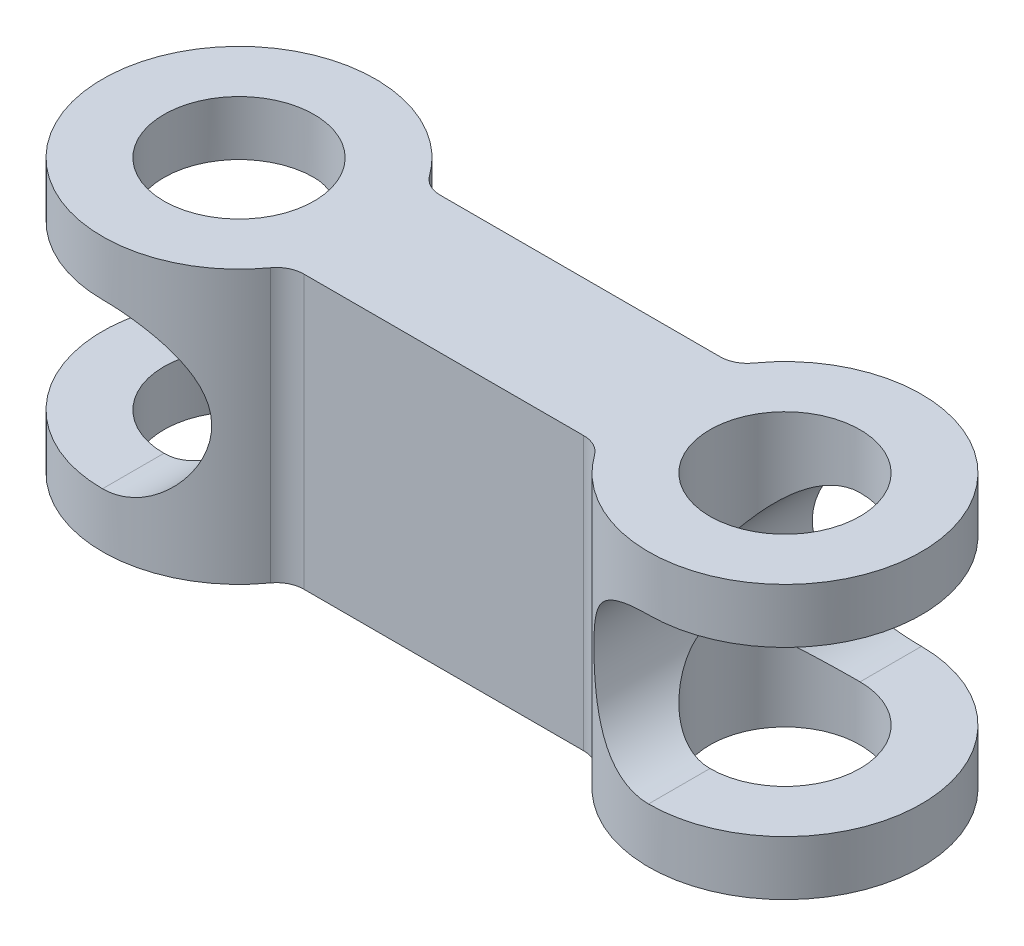
SolidWorks part; units mm, degrees
ref_plane "Front Plane" through (0, 0, 0) normal (0, 0, 1) x (1, 0, 0)
ref_plane "Top Plane" through (0, 0, 0) normal (0, 1, 0) x (1, 0, 0)
ref_plane "Right Plane" through (0, 0, 0) normal (1, 0, 0) x (0, 0, -1)
sketch "Sketch1" plane through (0, 0, 0) normal (0, 1, 0) x (1, 0, 0)
  line L1 (0, 2.5) -> (10, 2.5)
  line L2 (0, 2.5) -> (0, -2.5)
  line L3 (0, -2.5) -> (10, -2.5)
  line L4 (10, 2.5) -> (10, -2.5)
  dimension "D1" = 5
  dimension "D2" = 10
extrude "Boss-Extrude1" add sketch "Sketch1" along normal blind 10
sketch "Sketch2" plane through (0, 0, 0) normal (0, 1, 0) x (1, 0, 0)
  circle A0 centre (0, 0) radius 5
  dimension "D1" = 10
sketch "Sketch3" plane through (0, 0, 0) normal (0, 1, 0) x (1, 0, 0)
  circle A0 centre (0, 0) radius 2.75
  dimension "D1" = 5.5
extrude "Boss-Extrude2" add sketch "Sketch2" along normal up to surface (10 mm away) up to face at (5, 10, 0)
extrude "Cut-Extrude1" cut sketch "Sketch3" along normal up to next
sketch "Sketch4" plane through (0, 0, 0) normal (0, 0, 1) x (1, 0, 0)
  line L0 (0, 0) -> (0, 10) construction
  line L1 (2.75, 10) -> (-2.75, 10) construction
  line L2 (0, 8) -> (-5, 8)
  line L3 (-5, 10) -> (-5, 0) construction
  line L4 (0, 2) -> (-5, 2)
  line L5 (-5, 8) -> (-5, 2)
  arc A0 (0, 2) -> (0, 8) centre (0, 5) ccw
  dimension "D1" = 6
extrude "Cut-Extrude2" cut sketch "Sketch4" against normal through all both and the other way through all
fillet "Fillet1" radius 1 2 edges at (4.3301, 5, -2.5) (4.3301, 5, 2.5)
mirror "Mirror1" about plane through (10, 10, -2.5) normal (-1, 0, 0) of "Boss-Extrude1", "Cut-Extrude1", "Boss-Extrude2", "Cut-Extrude2", "Fillet1"
